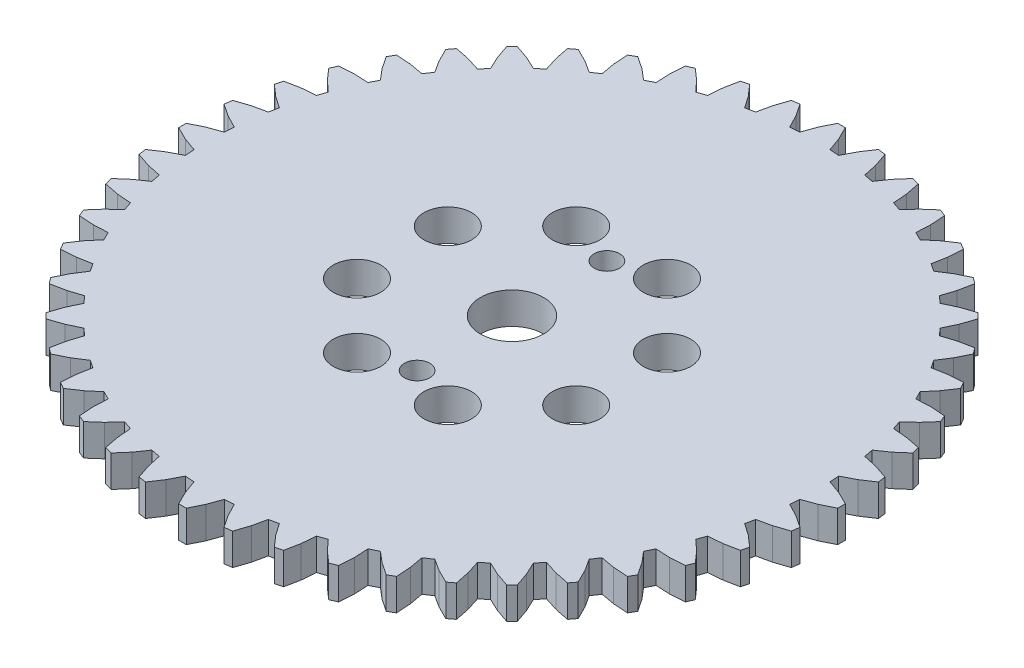
SolidWorks part; units mm, degrees
material "Acrylic (Medium-high impact)"
ref_plane "Front Plane" through (0, 0, 0) normal (0, 0, 1) x (1, 0, 0)
ref_plane "Top Plane" through (0, 0, 0) normal (0, 1, 0) x (1, 0, 0)
ref_plane "Right Plane" through (0, 0, 0) normal (1, 0, 0) x (0, 0, -1)
sketch "Sketch1" plane through (0, 0, 0) normal (0, 1, 0) x (1, 0, 0)
  line L0 (42.6708, 7.332) -> (44.3641, 6.7228)
  line L1 (44.3641, 6.7228) -> (46.0493, 5.8976)
  line L2 (46.0493, 5.8976) -> (46.0493, 4.9305)
  line L3 (46.0493, 4.9305) -> (44.3641, 4.1053)
  line L4 (44.3641, 4.1053) -> (42.6708, 3.4961)
  line L5 (42.6708, 3.4961) -> (42.5937, 2.3184)
  line L6 (42.5937, 2.3184) -> (44.1929, 1.4933)
  line L7 (44.1929, 1.4933) -> (45.7561, 0.4552)
  line L8 (45.7561, 0.4552) -> (45.6298, -0.5035)
  line L9 (45.6298, -0.5035) -> (43.8512, -1.1018)
  line L10 (43.8512, -1.1018) -> (42.093, -1.4848)
  line L11 (42.093, -1.4848) -> (41.8627, -2.6423)
  line L12 (41.8627, -2.6423) -> (43.3406, -3.669)
  line L13 (43.3406, -3.669) -> (44.7548, -4.9023)
  line L14 (44.7548, -4.9023) -> (44.5045, -5.8364)
  line L15 (44.5045, -5.8364) -> (42.663, -6.1973)
  line L16 (42.663, -6.1973) -> (40.8698, -6.3476)
  line L17 (40.8698, -6.3476) -> (40.4905, -7.4651)
  line L18 (40.4905, -7.4651) -> (41.8218, -8.676)
  line L19 (41.8218, -8.676) -> (43.0629, -10.0833)
  line L20 (43.0629, -10.0833) -> (42.6929, -10.9767)
  line L21 (42.6929, -10.9767) -> (40.82, -11.0943)
  line L22 (40.82, -11.0943) -> (39.0225, -11.0092)
  line L23 (39.0225, -11.0092) -> (38.5006, -12.0676)
  line L24 (38.5006, -12.0676) -> (39.6623, -13.4418)
  line L25 (39.6623, -13.4418) -> (40.7092, -14.9991)
  line L26 (40.7092, -14.9991) -> (40.2257, -15.8366)
  line L27 (40.2257, -15.8366) -> (38.3536, -15.7088)
  line L28 (38.3536, -15.7088) -> (36.5825, -15.3898)
  line L29 (36.5825, -15.3898) -> (35.9268, -16.371)
  line L30 (35.9268, -16.371) -> (36.8994, -17.8851)
  line L31 (36.8994, -17.8851) -> (37.734, -19.5657)
  line L32 (37.734, -19.5657) -> (37.1454, -20.3329)
  line L33 (37.1454, -20.3329) -> (35.3059, -19.9617)
  line L34 (35.3059, -19.9617) -> (33.5917, -19.4143)
  line L35 (33.5917, -19.4143) -> (32.8135, -20.3016)
  line L36 (32.8135, -20.3016) -> (33.58, -21.9296)
  line L37 (33.58, -21.9296) -> (34.1882, -23.7049)
  line L38 (34.1882, -23.7049) -> (33.5044, -24.3887)
  line L39 (33.5044, -24.3887) -> (31.7291, -23.7806)
  line L40 (31.7291, -23.7806) -> (30.1011, -23.014)
  line L41 (30.1011, -23.014) -> (29.2137, -23.7922)
  line L42 (29.2137, -23.7922) -> (29.7612, -25.5065)
  line L43 (29.7612, -25.5065) -> (30.1324, -27.3459)
  line L44 (30.1324, -27.3459) -> (29.3652, -27.9345)
  line L45 (29.3652, -27.9345) -> (27.6846, -27.0999)
  line L46 (27.6846, -27.0999) -> (26.1704, -26.1273)
  line L47 (26.1704, -26.1273) -> (25.1892, -26.783)
  line L48 (25.1892, -26.783) -> (25.5082, -28.5541)
  line L49 (25.5082, -28.5541) -> (25.6361, -30.4262)
  line L50 (25.6361, -30.4262) -> (24.7986, -30.9098)
  line L51 (24.7986, -30.9098) -> (23.2413, -29.8628)
  line L52 (23.2413, -29.8628) -> (21.8671, -28.7011)
  line L53 (21.8671, -28.7011) -> (20.8086, -29.223)
  line L54 (20.8086, -29.223) -> (20.8937, -31.0205)
  line L55 (20.8937, -31.0205) -> (20.7762, -32.8934)
  line L56 (20.7762, -32.8934) -> (19.8828, -33.2635)
  line L57 (19.8828, -33.2635) -> (18.4755, -32.0223)
  line L58 (18.4755, -32.0223) -> (17.2645, -30.691)
  line L59 (17.2645, -30.691) -> (16.147, -31.0704)
  line L60 (16.147, -31.0704) -> (15.9968, -32.8636)
  line L61 (15.9968, -32.8636) -> (15.6359, -34.7051)
  line L62 (15.6359, -34.7051) -> (14.7018, -34.9554)
  line L63 (14.7018, -34.9554) -> (13.4684, -33.5411)
  line L64 (13.4684, -33.5411) -> (12.4418, -32.0633)
  line L65 (12.4418, -32.0633) -> (11.2842, -32.2935)
  line L66 (11.2842, -32.2935) -> (10.9012, -34.0518)
  line L67 (10.9012, -34.0518) -> (10.303, -35.8303)
  line L68 (10.303, -35.8303) -> (9.3443, -35.9566)
  line L69 (9.3443, -35.9566) -> (8.3061, -34.3934)
  line L70 (8.3061, -34.3934) -> (7.4811, -32.7942)
  line L71 (7.4811, -32.7942) -> (6.3034, -32.8713)
  line L72 (6.3034, -32.8713) -> (5.6941, -34.5646)
  line L73 (5.6941, -34.5646) -> (4.869, -36.2498)
  line L74 (4.869, -36.2498) -> (3.9019, -36.2498)
  line L75 (3.9019, -36.2498) -> (3.0767, -34.5646)
  line L76 (3.0767, -34.5646) -> (2.4675, -32.8713)
  line L77 (2.4675, -32.8713) -> (1.2898, -32.7942)
  line L78 (1.2898, -32.7942) -> (0.4647, -34.3934)
  line L79 (0.4647, -34.3934) -> (-0.5735, -35.9566)
  line L80 (-0.5735, -35.9566) -> (-1.5322, -35.8303)
  line L81 (-1.5322, -35.8303) -> (-2.1304, -34.0518)
  line L82 (-2.1304, -34.0518) -> (-2.5134, -32.2935)
  line L83 (-2.5134, -32.2935) -> (-3.671, -32.0633)
  line L84 (-3.671, -32.0633) -> (-4.6976, -33.5411)
  line L85 (-4.6976, -33.5411) -> (-5.9309, -34.9554)
  line L86 (-5.9309, -34.9554) -> (-6.865, -34.7051)
  line L87 (-6.865, -34.7051) -> (-7.2259, -32.8636)
  line L88 (-7.2259, -32.8636) -> (-7.3762, -31.0704)
  line L89 (-7.3762, -31.0704) -> (-8.4937, -30.691)
  line L90 (-8.4937, -30.691) -> (-9.7047, -32.0223)
  line L91 (-9.7047, -32.0223) -> (-11.112, -33.2635)
  line L92 (-11.112, -33.2635) -> (-12.0054, -32.8934)
  line L93 (-12.0054, -32.8934) -> (-12.1229, -31.0205)
  line L94 (-12.1229, -31.0205) -> (-12.0378, -29.223)
  line L95 (-12.0378, -29.223) -> (-13.0963, -28.7011)
  line L96 (-13.0963, -28.7011) -> (-14.4705, -29.8628)
  line L97 (-14.4705, -29.8628) -> (-16.0278, -30.9098)
  line L98 (-16.0278, -30.9098) -> (-16.8653, -30.4262)
  line L99 (-16.8653, -30.4262) -> (-16.7374, -28.5541)
  line L100 (-16.7374, -28.5541) -> (-16.4184, -26.783)
  line L101 (-16.4184, -26.783) -> (-17.3996, -26.1273)
  line L102 (-17.3996, -26.1273) -> (-18.9137, -27.0999)
  line L103 (-18.9137, -27.0999) -> (-20.5944, -27.9345)
  line L104 (-20.5944, -27.9345) -> (-21.3616, -27.3459)
  line L105 (-21.3616, -27.3459) -> (-20.9903, -25.5065)
  line L106 (-20.9903, -25.5065) -> (-20.4429, -23.7922)
  line L107 (-20.4429, -23.7922) -> (-21.3303, -23.014)
  line L108 (-21.3303, -23.014) -> (-22.9583, -23.7806)
  line L109 (-22.9583, -23.7806) -> (-24.7335, -24.3887)
  line L110 (-24.7335, -24.3887) -> (-25.4174, -23.7049)
  line L111 (-25.4174, -23.7049) -> (-24.8092, -21.9296)
  line L112 (-24.8092, -21.9296) -> (-24.0427, -20.3016)
  line L113 (-24.0427, -20.3016) -> (-24.8209, -19.4143)
  line L114 (-24.8209, -19.4143) -> (-26.5351, -19.9617)
  line L115 (-26.5351, -19.9617) -> (-28.3745, -20.3329)
  line L116 (-28.3745, -20.3329) -> (-28.9632, -19.5657)
  line L117 (-28.9632, -19.5657) -> (-28.1286, -17.8851)
  line L118 (-28.1286, -17.8851) -> (-27.156, -16.371)
  line L119 (-27.156, -16.371) -> (-27.8117, -15.3898)
  line L120 (-27.8117, -15.3898) -> (-29.5827, -15.7088)
  line L121 (-29.5827, -15.7088) -> (-31.4549, -15.8366)
  line L122 (-31.4549, -15.8366) -> (-31.9384, -14.9991)
  line L123 (-31.9384, -14.9991) -> (-30.8915, -13.4418)
  line L124 (-30.8915, -13.4418) -> (-29.7297, -12.0676)
  line L125 (-29.7297, -12.0676) -> (-30.2516, -11.0092)
  line L126 (-30.2516, -11.0092) -> (-32.0492, -11.0943)
  line L127 (-32.0492, -11.0943) -> (-33.9221, -10.9767)
  line L128 (-33.9221, -10.9767) -> (-34.2921, -10.0833)
  line L129 (-34.2921, -10.0833) -> (-33.0509, -8.676)
  line L130 (-33.0509, -8.676) -> (-31.7197, -7.4651)
  line L131 (-31.7197, -7.4651) -> (-32.099, -6.3476)
  line L132 (-32.099, -6.3476) -> (-33.8922, -6.1973)
  line L133 (-33.8922, -6.1973) -> (-35.7337, -5.8364)
  line L134 (-35.7337, -5.8364) -> (-35.984, -4.9023)
  line L135 (-35.984, -4.9023) -> (-34.5698, -3.669)
  line L136 (-34.5698, -3.669) -> (-33.0919, -2.6423)
  line L137 (-33.0919, -2.6423) -> (-33.3222, -1.4848)
  line L138 (-33.3222, -1.4848) -> (-35.0804, -1.1018)
  line L139 (-35.0804, -1.1018) -> (-36.8589, -0.5035)
  line L140 (-36.8589, -0.5035) -> (-36.9853, 0.4552)
  line L141 (-36.9853, 0.4552) -> (-35.4221, 1.4933)
  line L142 (-35.4221, 1.4933) -> (-33.8228, 2.3184)
  line L143 (-33.8228, 2.3184) -> (-33.8999, 3.4961)
  line L144 (-33.8999, 3.4961) -> (-35.5933, 4.1053)
  line L145 (-35.5933, 4.1053) -> (-37.2785, 4.9305)
  line L146 (-37.2785, 4.9305) -> (-37.2785, 5.8976)
  line L147 (-37.2785, 5.8976) -> (-35.5933, 6.7228)
  line L148 (-35.5933, 6.7228) -> (-33.8999, 7.332)
  line L149 (-33.8999, 7.332) -> (-33.8228, 8.5097)
  line L150 (-33.8228, 8.5097) -> (-35.4221, 9.3348)
  line L151 (-35.4221, 9.3348) -> (-36.9853, 10.3729)
  line L152 (-36.9853, 10.3729) -> (-36.8589, 11.3316)
  line L153 (-36.8589, 11.3316) -> (-35.0804, 11.9299)
  line L154 (-35.0804, 11.9299) -> (-33.3222, 12.3129)
  line L155 (-33.3222, 12.3129) -> (-33.0919, 13.4704)
  line L156 (-33.0919, 13.4704) -> (-34.5698, 14.4971)
  line L157 (-34.5698, 14.4971) -> (-35.984, 15.7304)
  line L158 (-35.984, 15.7304) -> (-35.7337, 16.6645)
  line L159 (-35.7337, 16.6645) -> (-33.8922, 17.0254)
  line L160 (-33.8922, 17.0254) -> (-32.099, 17.1757)
  line L161 (-32.099, 17.1757) -> (-31.7197, 18.2932)
  line L162 (-31.7197, 18.2932) -> (-33.0509, 19.5041)
  line L163 (-33.0509, 19.5041) -> (-34.2921, 20.9114)
  line L164 (-34.2921, 20.9114) -> (-33.9221, 21.8048)
  line L165 (-33.9221, 21.8048) -> (-32.0492, 21.9224)
  line L166 (-32.0492, 21.9224) -> (-30.2516, 21.8373)
  line L167 (-30.2516, 21.8373) -> (-29.7297, 22.8957)
  line L168 (-29.7297, 22.8957) -> (-30.8915, 24.2699)
  line L169 (-30.8915, 24.2699) -> (-31.9384, 25.8272)
  line L170 (-31.9384, 25.8272) -> (-31.4549, 26.6647)
  line L171 (-31.4549, 26.6647) -> (-29.5827, 26.5368)
  line L172 (-29.5827, 26.5368) -> (-27.8117, 26.2178)
  line L173 (-27.8117, 26.2178) -> (-27.156, 27.1991)
  line L174 (-27.156, 27.1991) -> (-28.1286, 28.7132)
  line L175 (-28.1286, 28.7132) -> (-28.9632, 30.3938)
  line L176 (-28.9632, 30.3938) -> (-28.3745, 31.161)
  line L177 (-28.3745, 31.161) -> (-26.5351, 30.7898)
  line L178 (-26.5351, 30.7898) -> (-24.8209, 30.2424)
  line L179 (-24.8209, 30.2424) -> (-24.0427, 31.1297)
  line L180 (-24.0427, 31.1297) -> (-24.8092, 32.7577)
  line L181 (-24.8092, 32.7577) -> (-25.4174, 34.533)
  line L182 (-25.4174, 34.533) -> (-24.7335, 35.2168)
  line L183 (-24.7335, 35.2168) -> (-22.9583, 34.6087)
  line L184 (-22.9583, 34.6087) -> (-21.3303, 33.8421)
  line L185 (-21.3303, 33.8421) -> (-20.4429, 34.6203)
  line L186 (-20.4429, 34.6203) -> (-20.9903, 36.3346)
  line L187 (-20.9903, 36.3346) -> (-21.3616, 38.174)
  line L188 (-21.3616, 38.174) -> (-20.5944, 38.7626)
  line L189 (-20.5944, 38.7626) -> (-18.9137, 37.928)
  line L190 (-18.9137, 37.928) -> (-17.3996, 36.9554)
  line L191 (-17.3996, 36.9554) -> (-16.4184, 37.6111)
  line L192 (-16.4184, 37.6111) -> (-16.7374, 39.3822)
  line L193 (-16.7374, 39.3822) -> (-16.8653, 41.2543)
  line L194 (-16.8653, 41.2543) -> (-16.0278, 41.7379)
  line L195 (-16.0278, 41.7379) -> (-14.4705, 40.6909)
  line L196 (-14.4705, 40.6909) -> (-13.0963, 39.5292)
  line L197 (-13.0963, 39.5292) -> (-12.0378, 40.0511)
  line L198 (-12.0378, 40.0511) -> (-12.1229, 41.8486)
  line L199 (-12.1229, 41.8486) -> (-12.0054, 43.7215)
  line L200 (-12.0054, 43.7215) -> (-11.112, 44.0916)
  line L201 (-11.112, 44.0916) -> (-9.7047, 42.8504)
  line L202 (-9.7047, 42.8504) -> (-8.4937, 41.5191)
  line L203 (-8.4937, 41.5191) -> (-7.3762, 41.8985)
  line L204 (-7.3762, 41.8985) -> (-7.2259, 43.6917)
  line L205 (-7.2259, 43.6917) -> (-6.865, 45.5332)
  line L206 (-6.865, 45.5332) -> (-5.9309, 45.7835)
  line L207 (-5.9309, 45.7835) -> (-4.6976, 44.3692)
  line L208 (-4.6976, 44.3692) -> (-3.671, 42.8914)
  line L209 (-3.671, 42.8914) -> (-2.5134, 43.1216)
  line L210 (-2.5134, 43.1216) -> (-2.1304, 44.8799)
  line L211 (-2.1304, 44.8799) -> (-1.5322, 46.6584)
  line L212 (-1.5322, 46.6584) -> (-0.5735, 46.7847)
  line L213 (-0.5735, 46.7847) -> (0.4647, 45.2215)
  line L214 (0.4647, 45.2215) -> (1.2898, 43.6223)
  line L215 (1.2898, 43.6223) -> (2.4675, 43.6994)
  line L216 (2.4675, 43.6994) -> (3.0767, 45.3927)
  line L217 (3.0767, 45.3927) -> (3.9019, 47.0779)
  line L218 (3.9019, 47.0779) -> (4.869, 47.0779)
  line L219 (4.869, 47.0779) -> (5.6941, 45.3927)
  line L220 (5.6941, 45.3927) -> (6.3034, 43.6994)
  line L221 (6.3034, 43.6994) -> (7.4811, 43.6223)
  line L222 (7.4811, 43.6223) -> (8.3061, 45.2215)
  line L223 (8.3061, 45.2215) -> (9.3443, 46.7847)
  line L224 (9.3443, 46.7847) -> (10.303, 46.6584)
  line L225 (10.303, 46.6584) -> (10.9012, 44.8799)
  line L226 (10.9012, 44.8799) -> (11.2842, 43.1216)
  line L227 (11.2842, 43.1216) -> (12.4418, 42.8914)
  line L228 (12.4418, 42.8914) -> (13.4684, 44.3692)
  line L229 (13.4684, 44.3692) -> (14.7018, 45.7835)
  line L230 (14.7018, 45.7835) -> (15.6359, 45.5332)
  line L231 (15.6359, 45.5332) -> (15.9968, 43.6917)
  line L232 (15.9968, 43.6917) -> (16.147, 41.8985)
  line L233 (16.147, 41.8985) -> (17.2645, 41.5191)
  line L234 (17.2645, 41.5191) -> (18.4755, 42.8504)
  line L235 (18.4755, 42.8504) -> (19.8828, 44.0916)
  line L236 (19.8828, 44.0916) -> (20.7762, 43.7215)
  line L237 (20.7762, 43.7215) -> (20.8937, 41.8486)
  line L238 (20.8937, 41.8486) -> (20.8086, 40.0511)
  line L239 (20.8086, 40.0511) -> (21.8671, 39.5292)
  line L240 (21.8671, 39.5292) -> (23.2413, 40.6909)
  line L241 (23.2413, 40.6909) -> (24.7986, 41.7379)
  line L242 (24.7986, 41.7379) -> (25.6361, 41.2543)
  line L243 (25.6361, 41.2543) -> (25.5082, 39.3822)
  line L244 (25.5082, 39.3822) -> (25.1892, 37.6111)
  line L245 (25.1892, 37.6111) -> (26.1704, 36.9554)
  line L246 (26.1704, 36.9554) -> (27.6846, 37.928)
  line L247 (27.6846, 37.928) -> (29.3652, 38.7626)
  line L248 (29.3652, 38.7626) -> (30.1324, 38.174)
  line L249 (30.1324, 38.174) -> (29.7612, 36.3346)
  line L250 (29.7612, 36.3346) -> (29.2137, 34.6203)
  line L251 (29.2137, 34.6203) -> (30.1011, 33.8421)
  line L252 (30.1011, 33.8421) -> (31.7291, 34.6087)
  line L253 (31.7291, 34.6087) -> (33.5044, 35.2168)
  line L254 (33.5044, 35.2168) -> (34.1882, 34.533)
  line L255 (34.1882, 34.533) -> (33.58, 32.7577)
  line L256 (33.58, 32.7577) -> (32.8135, 31.1297)
  line L257 (32.8135, 31.1297) -> (33.5917, 30.2424)
  line L258 (33.5917, 30.2424) -> (35.3059, 30.7898)
  line L259 (35.3059, 30.7898) -> (37.1454, 31.161)
  line L260 (37.1454, 31.161) -> (37.734, 30.3938)
  line L261 (37.734, 30.3938) -> (36.8994, 28.7132)
  line L262 (36.8994, 28.7132) -> (35.9268, 27.1991)
  line L263 (35.9268, 27.1991) -> (36.5825, 26.2178)
  line L264 (36.5825, 26.2178) -> (38.3536, 26.5368)
  line L265 (38.3536, 26.5368) -> (40.2257, 26.6647)
  line L266 (40.2257, 26.6647) -> (40.7092, 25.8272)
  line L267 (40.7092, 25.8272) -> (39.6623, 24.2699)
  line L268 (39.6623, 24.2699) -> (38.5006, 22.8957)
  line L269 (38.5006, 22.8957) -> (39.0225, 21.8373)
  line L270 (39.0225, 21.8373) -> (40.82, 21.9224)
  line L271 (40.82, 21.9224) -> (42.6929, 21.8048)
  line L272 (42.6929, 21.8048) -> (43.0629, 20.9114)
  line L273 (43.0629, 20.9114) -> (41.8218, 19.5041)
  line L274 (41.8218, 19.5041) -> (40.4905, 18.2932)
  line L275 (40.4905, 18.2932) -> (40.8698, 17.1757)
  line L276 (40.8698, 17.1757) -> (42.663, 17.0254)
  line L277 (42.663, 17.0254) -> (44.5045, 16.6645)
  line L278 (44.5045, 16.6645) -> (44.7548, 15.7304)
  line L279 (44.7548, 15.7304) -> (43.3406, 14.4971)
  line L280 (43.3406, 14.4971) -> (41.8627, 13.4704)
  line L281 (41.8627, 13.4704) -> (42.093, 12.3129)
  line L282 (42.093, 12.3129) -> (43.8512, 11.9299)
  line L283 (43.8512, 11.9299) -> (45.6298, 11.3316)
  line L284 (45.6298, 11.3316) -> (45.7561, 10.3729)
  line L285 (45.7561, 10.3729) -> (44.1929, 9.3348)
  line L286 (44.1929, 9.3348) -> (42.5937, 8.5097)
  line L287 (42.5937, 8.5097) -> (42.6708, 7.332)
  line L288 (4.3854, 47.0779) -> (4.3854, -36.2498) construction
  line L289 (-37.2785, 5.414) -> (46.0493, 5.414) construction
  point P292 (4.3854, 5.414)
sketch "Sketch3" plane through (0, 0, 0) normal (0, 1, 0) x (1, 0, 0)
  line L0 (-37.2785, 5.414) -> (46.0493, 5.414) construction
  circle A0 centre (4.3854, 5.414) radius 4
  dimension "D1" = 8
sketch "Sketch4" plane through (0, 0, 0) normal (0, 1, 0) x (1, 0, 0)
  line L0 (-12.0218, 5.414) -> (22.4064, 5.414) construction
  line L1 (-37.2785, 5.414) -> (46.0493, 5.414) construction
  line L2 (4.3854, 47.0779) -> (4.3854, -36.2498) construction
  circle A0 centre (4.3854, 17.414) radius 1.6
  circle A1 centre (4.3854, -6.586) radius 1.6
  dimension "D1" = 3.2
  dimension "D2" = 12
extrude "Boss-Extrude2" add sketch "Sketch1" along normal blind 4
extrude "Cut-Extrude1" cut sketch "Sketch3" along normal up to next
extrude "Cut-Extrude2" cut sketch "Sketch4" along normal up to next
sketch "Sketch5" plane through (0, 0, 0) normal (0, 1, 0) x (1, 0, 0)
  line L0 (4.3854, 5.414) -> (4.3854, 47.0779) construction
  line L1 (4.869, 47.0779) -> (3.9019, 47.0779) construction
  line L2 (4.3854, 5.414) -> (22.1331, 48.2608) construction
  circle A0 centre (10.1257, 19.2722) radius 3
  point P0 (4.3854, 5.414)
  dimension "D2" = 6
  dimension "D1" = 22.5
  dimension "D3" = 15
extrude "Cut-Extrude3" cut sketch "Sketch5" along normal up to next
pattern_circular "CirPattern1" count 8 over 360 about axis through (4.3854, 4, -5.414) along (0, -1, 0) of "Cut-Extrude3"
